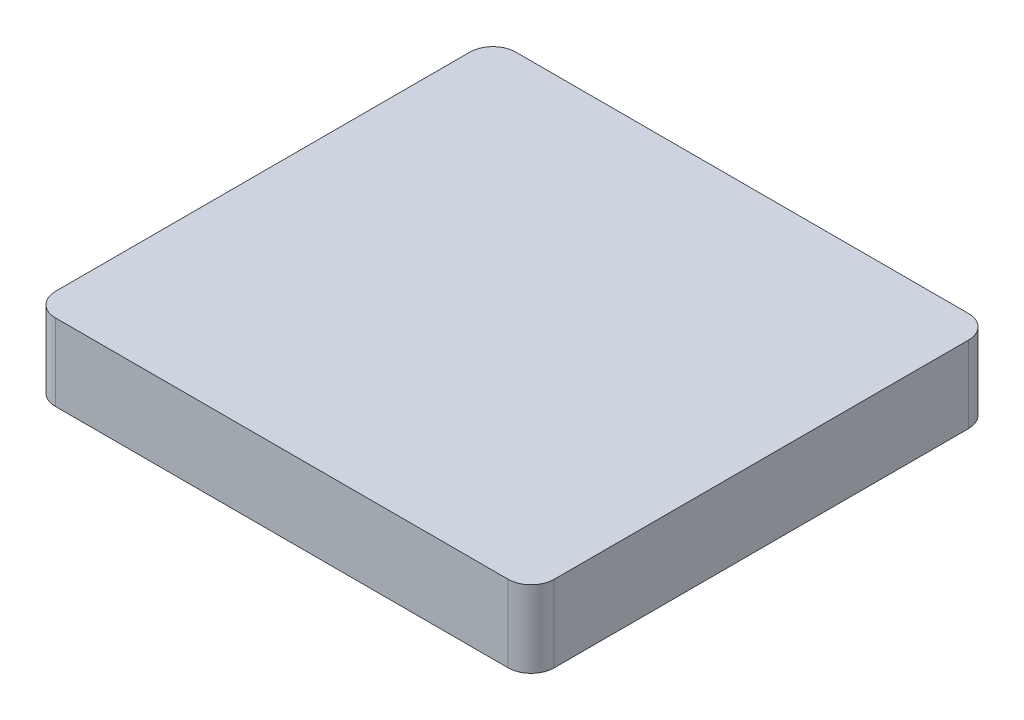
SolidWorks part; units mm, degrees
ref_plane "前视基准面" through (0, 0, 0) normal (0, 0, 1) x (1, 0, 0)
ref_plane "上视基准面" through (0, 0, 0) normal (0, 1, 0) x (1, 0, 0)
ref_plane "右视基准面" through (0, 0, 0) normal (1, 0, 0) x (0, 0, -1)
sketch "草图1" plane through (0, 0, 0) normal (0, 1, 0) x (1, 0, 0)
  line L1 (-32.5, 30) -> (32.5, 30)
  line L2 (-32.5, 30) -> (-32.5, -30)
  line L3 (-32.5, -30) -> (32.5, -30)
  line L4 (32.5, 30) -> (32.5, -30)
  line L5 (-32.5, 30) -> (32.5, -30) construction
  line L6 (-32.5, -30) -> (32.5, 30) construction
  point P0 (0, 0)
  dimension "D1" = 60
  dimension "D2" = 65
extrude "凸台-拉伸1" add sketch "草图1" along normal blind 10
fillet "圆角1" radius 3 4 edges at (-32.5, 5, -30) (32.5, 5, -30) (32.5, 5, 30) (-32.5, 5, 30)
